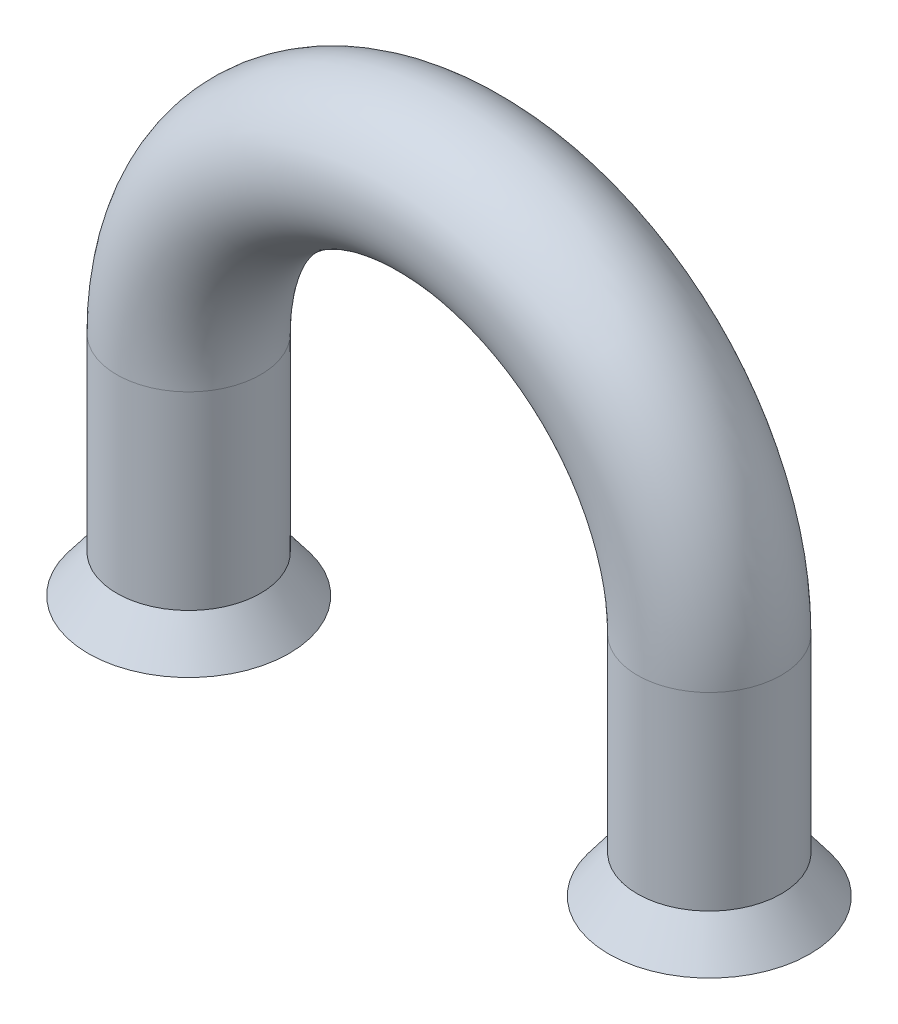
SolidWorks part; units mm, degrees
material "6061-T6 (SS)"
ref_plane "Front Plane" through (0, 0, 0) normal (0, 0, 1) x (1, 0, 0)
ref_plane "Top Plane" through (0, 0, 0) normal (0, 1, 0) x (1, 0, 0)
ref_plane "Right Plane" through (0, 0, 0) normal (1, 0, 0) x (0, 0, -1)
sketch "Sketch1" plane through (0, 0, 0) normal (0, 1, 0) x (1, 0, 0)
  circle A0 centre (0, 0) radius 4.826
  circle A1 centre (0, 0) radius 4.064
  dimension "D1" = 9.652
  dimension "D2" = 8.128
sketch "Sketch2" plane through (0, 0, 0) normal (0, 0, 1) x (1, 0, 0)
  line L0 (0, 0) -> (0, 12.7)
  line L1 (34.925, 12.7) -> (34.925, 0)
  arc A0 (0, 12.7) -> (34.925, 12.7) centre (17.4625, 12.7) cw
  dimension "D1" = 12.7
  dimension "D2" = 34.925
  dimension "D4" = 17.4625
sweep "Sweep1" add profiles "Sketch1" path "Sketch2"
sketch "Sketch3" plane through (0, 0, 0) normal (0, -1, 0) x (1, 0, 0)
  circle A0 centre (0, 0) radius 4.826
  circle A1 centre (0, 0) radius 4.826 construction
extrude "Boss-Extrude1" add sketch "Sketch3" along normal blind 2.54 draft 37 draft outward yes
sketch "Sketch4" plane through (0, -2.54, 0) normal (0, -1, 0) x (1, 0, 0)
  line L0 (-4.826, 0) -> (-4.064, 0) construction
  line L1 (-5.978, 0) -> (-6.74, 0) construction
  circle A0 centre (0, 0) radius 5.978
  circle A1 centre (0, 0) radius 4.826 construction
  circle A2 centre (0, 0) radius 4.064 construction
  circle A3 centre (0, 0) radius 6.74 construction
extrude "Cut-Extrude1" cut sketch "Sketch4" against normal through all draft 37
sketch "Sketch5" plane through (0, 0, 0) normal (0, -1, 0) x (0, 0, -1)
  circle A1 centre (0, 34.925) radius 4.826
  circle A4 centre (0, 34.925) radius 4.826 construction
extrude "Boss-Extrude2" add sketch "Sketch5" along normal blind 2.54 draft 37 draft outward yes
sketch "Sketch6" plane through (0, -2.54, 0) normal (0, -1, 0) x (0, 0, -1)
  line L0 (-5.978, 34.925) -> (-6.74, 34.925) construction
  circle A0 centre (0, 34.925) radius 5.978
  circle A1 centre (0, 34.925) radius 6.74 construction
  dimension "D1" = 0.762
extrude "Cut-Extrude2" cut sketch "Sketch6" against normal through all draft 37
